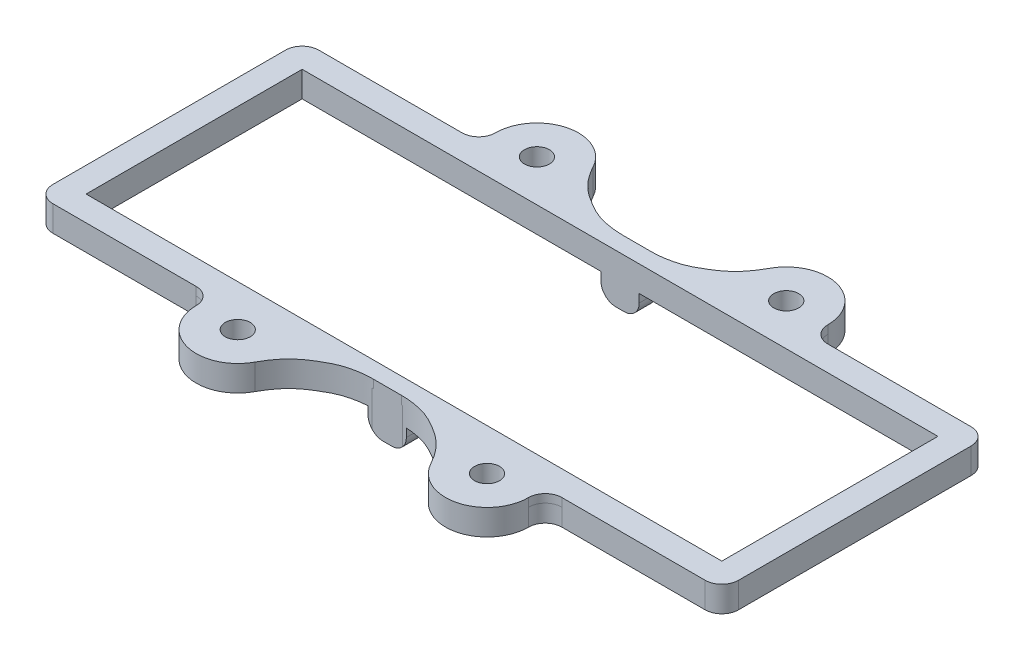
SolidWorks part; units mm, degrees
ref_plane "Front Plane" through (0, 0, 0) normal (0, 0, 1) x (1, 0, 0)
ref_plane "Top Plane" through (0, 0, 0) normal (0, 1, 0) x (1, 0, 0)
ref_plane "Right Plane" through (0, 0, 0) normal (1, 0, 0) x (0, 0, -1)
sketch "Sketch1" plane through (0, 0, 0) normal (0, 1, 0) x (1, 0, 0)
  line L0 (-44.593, 3.4751) -> (37.907, 3.4751) construction
  line L1 (-44.593, 19.4751) -> (37.907, 19.4751)
  line L2 (-44.593, 19.4751) -> (-44.593, -12.5249)
  line L3 (-44.593, -12.5249) -> (37.907, -12.5249)
  line L4 (37.907, 19.4751) -> (37.907, -12.5249)
  line L5 (-41.593, 16.4751) -> (34.907, 16.4751)
  line L6 (-41.593, 16.4751) -> (-41.593, -9.5249)
  line L7 (-41.593, -9.5249) -> (34.907, -9.5249)
  line L8 (34.907, 16.4751) -> (34.907, -9.5249)
  line L9 (-3.343, 19.4751) -> (-3.343, -12.5249) construction
  line L10 (16.657, -12.5249) -> (16.657, -19.5249)
  line L11 (-23.343, 19.4751) -> (16.657, 19.4751)
  line L12 (-23.343, 19.4751) -> (-23.343, 26.4751)
  line L13 (-23.343, 26.4751) -> (16.657, 26.4751)
  line L14 (16.657, 19.4751) -> (16.657, 26.4751)
  line L15 (-23.343, -19.5249) -> (16.657, -19.5249)
  line L16 (-23.343, -12.5249) -> (-23.343, -19.5249)
  line L17 (-23.343, -12.5249) -> (16.657, -12.5249)
  line L18 (-25.2775, 21.4751) -> (22.0201, 21.4751) construction
  circle A0 centre (-18.343, 21.4751) radius 1.5
  circle A1 centre (11.657, 21.4751) radius 1.5
  circle A2 centre (11.657, -14.5249) radius 1.5
  circle A3 centre (-18.343, -14.5249) radius 1.5
  dimension "D1" = 82.5
  dimension "D2" = 32
  dimension "D3" = 76.5
  dimension "D4" = 26
  dimension "D5" = 13
  dimension "D6" = 38.25
  dimension "D7" = 40
  dimension "D8" = 20
  dimension "D9" = 7
  dimension "D10" = 30
  dimension "D12" = 15
  dimension "D13" = 2
extrude "Boss-Extrude1" add sketch "Sketch1" along normal blind 2.085 contours L3 L16 L15 L10 A2 A3 | L4 L1 L2 L3 L5 L8 L7 L6 | L1 L14 L13 L12 A1 A0
sketch "Sketch2" plane through (0, 0, 0) normal (0, -1, 0) x (1, 0, 0)
  line L0 (-3.343, 19.5249) -> (-3.343, -26.4751) construction
  line L1 (-23.343, 19.5249) -> (16.657, 19.5249) construction
  line L2 (-23.343, -26.4751) -> (16.657, -26.4751) construction
  line L3 (-41.593, -3.4751) -> (34.907, -3.4751) construction
  line L4 (-5.843, 19.5249) -> (-0.843, 19.5249)
  line L5 (-5.843, 19.5249) -> (-5.843, 9.5249)
  line L6 (-5.843, 9.5249) -> (-0.843, 9.5249)
  line L7 (-0.843, 19.5249) -> (-0.843, 9.5249)
  line L8 (-41.593, -16.4751) -> (-41.593, 9.5249) construction
  line L9 (34.907, -16.4751) -> (34.907, 9.5249) construction
  line L10 (-0.843, -26.4751) -> (-0.843, -16.4751)
  line L11 (-5.843, -16.4751) -> (-0.843, -16.4751)
  line L12 (-5.843, -26.4751) -> (-5.843, -16.4751)
  line L13 (-5.843, -26.4751) -> (-0.843, -26.4751)
  dimension "D1" = 5
  dimension "D2" = 10
  dimension "D3" = 2.5
extrude "Boss-Extrude2" add sketch "Sketch2" along normal blind 3
fillet "Fillet1" radius 2 4 edges at (-5.843, -3, 14.5249) (-0.843, -3, 14.5249) (-0.843, -3, -21.4751) (-5.843, -3, -21.4751)
fillet "Fillet2" radius 2 4 edges at (-44.593, 1.0425, 12.5249) (-44.593, 1.0425, -19.4751) (37.907, 1.0425, -19.4751) (37.907, 1.0425, 12.5249)
sketch "Sketch3" plane through (0, 0, -26.4751) normal (0, 0, -1) x (-1, 0, 0)
  line L8 (23.343, 0) -> (5.843, 0) construction
  line L9 (6.1655, 0) -> (0.1244, 0)
  line L10 (6.1655, 0) -> (6.1655, -3.3793)
  line L11 (6.1655, -3.3793) -> (0.1244, -3.3793)
  line L12 (0.1244, 0) -> (0.1244, -3.3793)
  line L16 (2.843, -2.8) -> (3.843, -2.8)
  line L17 (5.643, 0.2) -> (23.143, 0.2)
  line L18 (23.143, 0.2) -> (23.143, 1.885)
  line L19 (23.143, 1.885) -> (-16.457, 1.885)
  line L20 (-16.457, 1.885) -> (-16.457, 0.2)
  line L21 (-16.457, 0.2) -> (1.043, 0.2)
  line L22 (2.843, -2.8) -> (3.843, -2.8)
  line L23 (5.643, 0.2) -> (23.143, 0.2)
  line L24 (23.143, 0.2) -> (23.143, 1.885)
  line L25 (23.143, 1.885) -> (-16.457, 1.885)
  line L26 (-16.457, 1.885) -> (-16.457, 0.2)
  line L27 (-16.457, 0.2) -> (1.043, 0.2)
  line L28 (1.043, 0.2) -> (1.043, -1)
  line L29 (1.043, 0.2) -> (1.043, -1)
  line L30 (5.643, -1) -> (5.643, 0.2)
  line L31 (5.643, -1) -> (5.643, 0.2)
  arc A4 (1.043, -1) -> (2.843, -2.8) centre (2.843, -1) ccw
  arc A5 (3.843, -2.8) -> (5.643, -1) centre (3.843, -1) ccw
  arc A6 (1.043, -1) -> (2.843, -2.8) centre (2.843, -1) ccw
  arc A7 (3.843, -2.8) -> (5.643, -1) centre (3.843, -1) ccw
  line M11 (0.843, 0) -> (0.843, -1)
  arc M12 (0.843, -1) -> (2.843, -3) centre (2.843, -1) ccw
  line M13 (2.843, -3) -> (3.843, -3)
  arc M14 (3.843, -3) -> (5.843, -1) centre (3.843, -1) ccw
  line M15 (5.843, -1) -> (5.843, 0)
  dimension "D1" = 0.2
extrude "Cut-Extrude1" cut sketch "Sketch3" against normal through all contours A7 L22 A6 L29 L9 L31 M11 M12 M13 M14 M15
sketch "Sketch4" plane through (0, 2.085, 0) normal (0, 1, 0) x (1, 0, 0)
  line L0 (-3.343, 18.4751) -> (7.657, 18.4751)
  line L1 (7.657, 18.4751) -> (-14.343, 18.4751)
  line L2 (-5.0256, 18.4751) -> (-1.6603, 18.4751)
  line L3 (37.907, 3.4751) -> (-44.593, 3.4751) construction
  line L4 (37.907, 17.4751) -> (37.907, -10.5249) construction
  line L5 (-44.593, 17.4751) -> (-44.593, -10.5249) construction
  line L6 (11.657, 26.4751) -> (11.657, 33.2921)
  line L7 (11.657, 33.2921) -> (-18.343, 33.2921)
  line L8 (-18.343, 33.2921) -> (-18.343, 26.4751)
  line L9 (-18.343, -26.342) -> (-18.343, -19.5249)
  line L10 (11.657, -26.342) -> (-18.343, -26.342)
  line L11 (11.657, -19.5249) -> (11.657, -26.342)
  line L12 (-5.0256, -11.5249) -> (-1.6603, -11.5249)
  line L13 (7.657, -11.5249) -> (-14.343, -11.5249)
  line L14 (-3.343, -11.5249) -> (7.657, -11.5249)
  circle A0 centre (-18.343, 21.4751) radius 5
  circle A1 centre (11.657, 21.4751) radius 5
  circle A2 centre (11.657, -14.5249) radius 5
  circle A3 centre (-18.343, -14.5249) radius 5
  spline S0 degree 3 poles (-13.9208, 23.8084) (-13.3837, 22.8069) (-12.2321, 21.2227) (-10.1423, 19.8877) (-8.5768, 19.0482) (-6.9016, 18.5983) (-5.7419, 18.469) (-5.0256, 18.4751) knots 0 0 0 0 0.314938 0.52444 0.679222 0.802825 1 1 1 1
  spline S1 degree 3 poles (7.2349, 23.8084) (6.6978, 22.8069) (5.5462, 21.2227) (3.4564, 19.8877) (1.8909, 19.0482) (0.2157, 18.5983) (-0.944, 18.469) (-1.6603, 18.4751) knots 0 0 0 0 0.314938 0.52444 0.679222 0.802825 1 1 1 1
  spline S2 degree 3 poles (7.2349, -16.8583) (6.6978, -15.8568) (5.5462, -14.2726) (3.4564, -12.9376) (1.8909, -12.0981) (0.2157, -11.6482) (-0.944, -11.5188) (-1.6603, -11.5249) knots 0 0 0 0 0.314938 0.52444 0.679222 0.802825 1 1 1 1
  spline S3 degree 3 poles (-13.9208, -16.8583) (-13.3837, -15.8568) (-12.2321, -14.2726) (-10.1423, -12.9376) (-8.5768, -12.0981) (-6.9016, -11.6482) (-5.7419, -11.5188) (-5.0256, -11.5249) knots 0 0 0 0 0.314938 0.52444 0.679222 0.802825 1 1 1 1
  line M7 (-23.343, -19.5249) -> (16.657, -19.5249)
  line M15 (16.657, 26.4751) -> (-23.343, 26.4751)
extrude "Cut-Extrude2" cut sketch "Sketch4" against normal through all contours S1 A1 A0 S0 L1 L0 M15 | L7 L8 L6 M15 | S3 A3 A2 S2 L14 L13 L12 M7 | L11 L9 L10 M7
fillet "Fillet3" radius 5 4 edges at (16.657, 1.0425, -26.4751) (-23.343, 1.0425, -26.4751) (-23.343, 1.0425, 19.5249) (16.657, 1.0425, 19.5249)
fillet "Fillet4" radius 2 12 edges at (16.657, 2.085, 13.5249) (-23.343, 0, 13.5249) (-23.343, 0, -20.4751) (16.657, 0, -20.4751) (16.657, 0, 13.5249) (16.657, 2.085, -20.4751) (-23.343, 1.0425, 12.5249) (-23.343, 1.0425, -19.4751) (16.657, 1.0425, -19.4751) (16.657, 1.0425, 12.5249) (-23.343, 2.085, -20.4751) (-23.343, 2.085, 13.5249)
sketch "Sketch5" plane through (0, 2.085, 0) normal (0, 1, 0) x (1, 0, 0)
  line L0 (-23.343, 21.4751) -> (-23.343, 16.4751)
  line L1 (-41.593, 3.4751) -> (34.907, 3.4751) construction
  line L2 (-41.593, 16.4751) -> (-41.593, -9.5249) construction
  line L3 (34.907, 16.4751) -> (34.907, -9.5249) construction
  line L4 (-3.343, -9.5249) -> (-3.343, 43.7071) construction
  line L5 (-41.593, 16.4751) -> (34.907, 16.4751) construction
  line L6 (-3.343, 18.4751) -> (7.657, 18.4751)
  line L7 (7.657, 18.4751) -> (-14.343, 18.4751)
  line L8 (-14.343, 18.4751) -> (-14.343, 31.9361)
  line L9 (-3.343, 18.4751) -> (-3.343, 35.8237) construction
  line L10 (-5.0256, 18.4751) -> (-1.6603, 18.4751)
  line L11 (-41.593, -9.5249) -> (34.907, -9.5249) construction
  line L12 (-23.343, 16.4751) -> (16.657, 16.4751)
  line L13 (16.657, 16.4751) -> (16.657, 21.4751)
  line L14 (16.657, -9.5249) -> (16.657, -14.5249)
  line L15 (-23.343, -9.5249) -> (16.657, -9.5249)
  line L16 (-5.0256, -11.5249) -> (-1.6603, -11.5249)
  line L17 (7.657, -11.5249) -> (-14.343, -11.5249)
  line L18 (-3.343, -11.5249) -> (7.657, -11.5249)
  line L19 (-23.343, -14.5249) -> (-23.343, -9.5249)
  line L21 (34.907, -9.5249) -> (-41.593, -9.5249)
  line L22 (34.907, -9.5249) -> (34.907, 16.4751)
  line L23 (34.907, 16.4751) -> (-41.593, 16.4751)
  line L24 (-41.593, -9.5249) -> (-41.593, 16.4751)
  line L25 (35.907, -12.5249) -> (-42.593, -12.5249)
  line L26 (37.907, -10.5249) -> (37.907, 17.4751)
  line L27 (35.907, 19.4751) -> (-42.593, 19.4751)
  line L28 (-44.593, -10.5249) -> (-44.593, 17.4751)
  circle A0 centre (-18.343, 21.4751) radius 5
  circle A1 centre (11.657, 21.4751) radius 5
  circle A2 centre (11.657, -14.5249) radius 5
  circle A3 centre (-18.343, -14.5249) radius 5
  arc A4 (-42.593, -12.5249) -> (-44.593, -10.5249) centre (-42.593, -10.5249) cw
  arc A5 (-42.593, 19.4751) -> (-44.593, 17.4751) centre (-42.593, 17.4751) ccw
  arc A6 (37.907, 17.4751) -> (35.907, 19.4751) centre (35.907, 17.4751) ccw
  arc A7 (35.907, -12.5249) -> (37.907, -10.5249) centre (35.907, -10.5249) ccw
  spline S0 degree 3 poles (-13.9208, 23.8084) (-13.3837, 22.8069) (-12.2321, 21.2227) (-10.1423, 19.8877) (-8.5768, 19.0482) (-6.9016, 18.5983) (-5.7419, 18.469) (-5.0256, 18.4751) knots 0 0 0 0 0.314938 0.52444 0.679222 0.802825 1 1 1 1
  spline S1 degree 3 poles (7.2349, 23.8084) (6.6978, 22.8069) (5.5462, 21.2227) (3.4564, 19.8877) (1.8909, 19.0482) (0.2157, 18.5983) (-0.944, 18.469) (-1.6603, 18.4751) knots 0 0 0 0 0.314938 0.52444 0.679222 0.802825 1 1 1 1
  spline S2 degree 3 poles (7.2349, -16.8583) (6.6978, -15.8568) (5.5462, -14.2726) (3.4564, -12.9376) (1.8909, -12.0981) (0.2157, -11.6482) (-0.944, -11.5188) (-1.6603, -11.5249) knots 0 0 0 0 0.314938 0.52444 0.679222 0.802825 1 1 1 1
  spline S3 degree 3 poles (-13.9208, -16.8583) (-13.3837, -15.8568) (-12.2321, -14.2726) (-10.1423, -12.9376) (-8.5768, -12.0981) (-6.9016, -11.6482) (-5.7419, -11.5188) (-5.0256, -11.5249) knots 0 0 0 0 0.314938 0.52444 0.679222 0.802825 1 1 1 1
  circle M5 centre (-18.343, 21.4751) radius 1.5
  circle M6 centre (11.657, 21.4751) radius 1.5
  line M7 (-41.593, 16.4751) -> (34.907, 16.4751)
  line M8 (34.907, 16.4751) -> (34.907, -9.5249)
  line M9 (34.907, -9.5249) -> (-41.593, -9.5249)
  line M10 (-41.593, -9.5249) -> (-41.593, 16.4751)
  circle M11 centre (-18.343, -14.5249) radius 1.5
  circle M12 centre (11.657, -14.5249) radius 1.5
  line M13 (35.907, 19.4751) -> (18.657, 19.4751)
  arc M15 (16.657, 21.4751) -> (11.657, 26.4751) centre (11.657, 21.4751) ccw
  arc M16 (11.657, 26.4751) -> (7.2349, 23.8084) centre (11.657, 21.4751) ccw
  spline M17 degree 3 poles (7.2349, 23.8084) (6.6978, 22.8069) (5.5462, 21.2227) (3.4564, 19.8877) (1.8909, 19.0482) (0.2157, 18.5983) (-0.944, 18.469) (-1.6603, 18.4751) knots 0 0 0 0 0.314938 0.52444 0.679222 0.802825 1 1 1 1 only from (7.2349, 23.8084) to (-1.5064, 18.4751)
  line M18 (-1.5064, 18.4751) -> (-5.1795, 18.4751)
  spline M19 degree 3 poles (-5.0256, 18.4751) (-5.7419, 18.469) (-6.9016, 18.5983) (-8.5768, 19.0482) (-10.1423, 19.8877) (-12.2321, 21.2227) (-13.3837, 22.8069) (-13.9208, 23.8084) knots 0 0 0 0 0.197175 0.320778 0.47556 0.685062 1 1 1 1 only from (-5.1795, 18.4751) to (-13.9208, 23.8084)
  arc M20 (-13.9208, 23.8084) -> (-18.343, 26.4751) centre (-18.343, 21.4751) ccw
  arc M21 (-18.343, 26.4751) -> (-23.343, 21.4751) centre (-18.343, 21.4751) ccw
  line M23 (-25.343, 19.4751) -> (-42.593, 19.4751)
  arc M24 (-42.593, 19.4751) -> (-44.593, 17.4751) centre (-42.593, 17.4751) ccw
  line M25 (-44.593, 17.4751) -> (-44.593, -10.5249)
  arc M26 (-44.593, -10.5249) -> (-42.593, -12.5249) centre (-42.593, -10.5249) ccw
  line M27 (-42.593, -12.5249) -> (-25.343, -12.5249)
  arc M29 (-23.343, -14.5249) -> (-18.343, -19.5249) centre (-18.343, -14.5249) ccw
  arc M30 (-18.343, -19.5249) -> (-13.9208, -16.8583) centre (-18.343, -14.5249) ccw
  spline M31 degree 3 poles (-13.9208, -16.8583) (-13.3837, -15.8568) (-12.2321, -14.2726) (-10.1423, -12.9376) (-8.5768, -12.0981) (-6.9016, -11.6482) (-5.7419, -11.5188) (-5.0256, -11.5249) knots 0 0 0 0 0.314938 0.52444 0.679222 0.802825 1 1 1 1 only from (-13.9208, -16.8583) to (-5.1795, -11.5249)
  line M32 (-5.1795, -11.5249) -> (-1.5064, -11.5249)
  spline M33 degree 3 poles (-1.6603, -11.5249) (-0.944, -11.5188) (0.2157, -11.6482) (1.8909, -12.0981) (3.4564, -12.9376) (5.5462, -14.2726) (6.6978, -15.8568) (7.2349, -16.8583) knots 0 0 0 0 0.197175 0.320778 0.47556 0.685062 1 1 1 1 only from (-1.5064, -11.5249) to (7.2349, -16.8583)
  arc M34 (7.2349, -16.8583) -> (11.657, -19.5249) centre (11.657, -14.5249) ccw
  arc M35 (11.657, -19.5249) -> (16.657, -14.5249) centre (11.657, -14.5249) ccw
  line M37 (18.657, -12.5249) -> (35.907, -12.5249)
  arc M38 (35.907, -12.5249) -> (37.907, -10.5249) centre (35.907, -10.5249) ccw
  line M39 (37.907, -10.5249) -> (37.907, 17.4751)
  arc M40 (37.907, 17.4751) -> (35.907, 19.4751) centre (35.907, 17.4751) ccw
  dimension "D1" = 2
extrude "Boss-Extrude3" add sketch "Sketch5" along normal blind 1 contours A0 L8 M20 M21 M5 | L6 S1 L7 S0 A0 L12 A1 M18 | A0 L0 M7 | L8 A0 M20 | A0 L7 M19 | A1 L6 M17 | A1 M15 M16 M6 | A1 L13 M7 | L19 A3 M9 | A3 M29 M30 M11 | L17 S3 S2 A2 L15 A3 M32 | L17 A3 M31 | A2 L17 M33 | A2 M34 M35 M12 | A2 L14 M9 | L27 L13 L14 L25 M13 M7 M8 M9 M37 M38 M39 M40 | L0 L27 L25 L19 M23 M24 M25 M26 M27 M9 M10 M7 | A2 L25 | A2 L25 M33 | A3 L25 | L25 A3 M31 | A1 L27 | A1 L27 M17 | A0 L8 L27 | A0 L27 M19 | L8 A0 L27
fillet "Fillet5" radius 2 12 edges at (16.2396, 2.585, 12.5249) (17.4483, 2.085, -19.4751) (16.5516, 2.085, -20.4535) (16.2396, 2.585, -19.4751) (-23.2375, 2.085, -20.4535) (-24.1342, 2.085, -19.4751) (-22.9255, 2.585, -19.4751) (-24.1342, 2.085, 12.5249) (-22.9255, 2.585, 12.5249) (-23.2375, 2.085, 13.5034) (17.4483, 2.085, 12.5249) (16.5516, 2.085, 13.5034)
